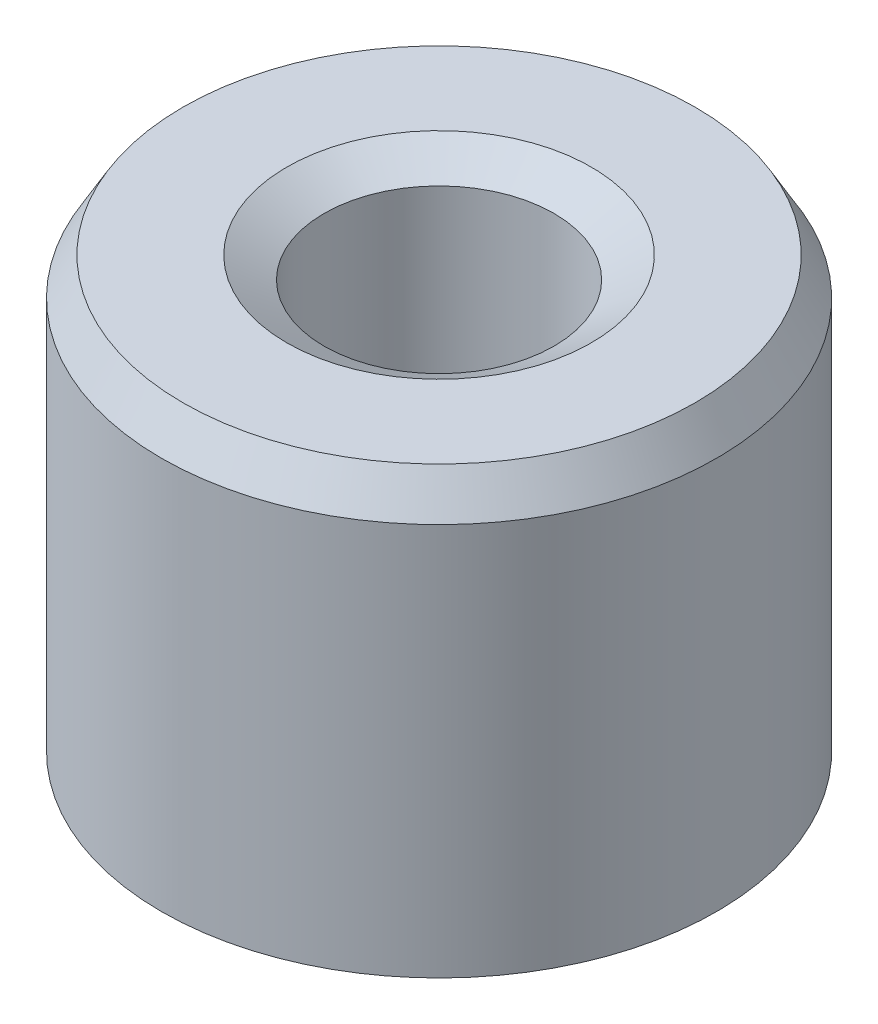
SolidWorks part; units mm, degrees
ref_plane "Front Plane" through (0, 0, 0) normal (0, 0, 1) x (1, 0, 0)
ref_plane "Top Plane" through (0, 0, 0) normal (0, 1, 0) x (1, 0, 0)
ref_plane "Right Plane" through (0, 0, 0) normal (1, 0, 0) x (0, 0, -1)
sketch "Sketch1" plane through (0, 0, 0) normal (0, 1, 0) x (1, 0, 0)
  circle A0 centre (0, 0) radius 25
  dimension "SLEEVE_OD" = 50
extrude "Boss-Extrude1" add sketch "Sketch1" along normal blind 40.6519
sketch "Sketch2" plane through (0, 0, 0) normal (0, 1, 0) x (1, 0, 0)
  circle A0 centre (0, 0) radius 10.3557
  dimension "BORE_D" = 20.7114
extrude "Cut-Extrude1" cut sketch "Sketch2" along normal through all
chamfer "Chamfer1" distance 3.3566 angle 30 4 edges at (0, 40.6519, 10.3557) (0, 0, 10.3557) (0, 0, 25) (0, 40.6519, 25) first distance on face at (0, 40.6519, 10.3557) first distance on face at (0, 0, 10.3557) first distance on face at (0, 40.6519, 25)
